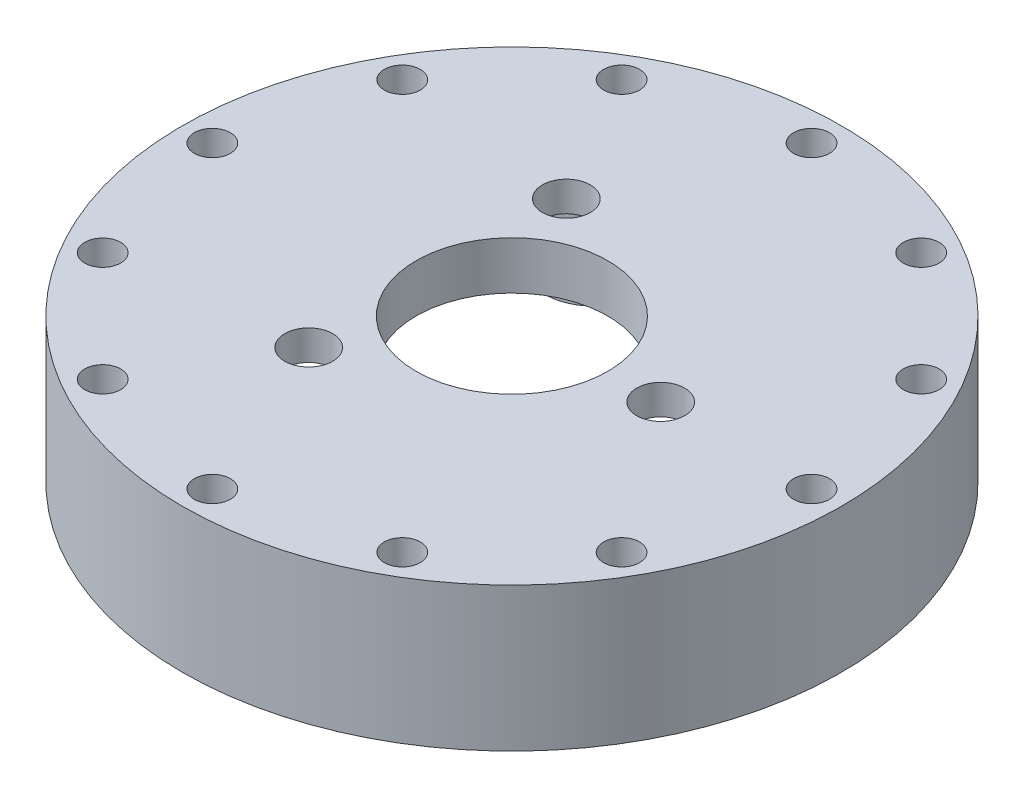
SolidWorks part; units mm, degrees
ref_plane "Front Plane" through (0, 0, 0) normal (0, 0, 1) x (1, 0, 0)
ref_plane "Top Plane" through (0, 0, 0) normal (0, 1, 0) x (1, 0, 0)
ref_plane "Right Plane" through (0, 0, 0) normal (1, 0, 0) x (0, 0, -1)
sketch "Sketch1" plane through (0, 0, 0) normal (0, 1, 0) x (1, 0, 0)
  line L0 (0, 22.5) -> (0, 0) construction
  line L1 (0, 0) -> (12.1644, 18.9282) construction
  line L2 (0, 0) -> (-12.1644, 18.9282) construction
  line L3 (-20.4667, 9.3468) -> (0, 0) construction
  line L4 (0, 0) -> (-22.271, -3.2021) construction
  circle A0 centre (0, 0) radius 22.5
  circle A1 centre (0, 0) radius 27.5
  circle A2 centre (0, 22.5) radius 4
  circle A3 centre (12.1644, 18.9282) radius 4
  circle A4 centre (20.4667, 9.3468) radius 4
  circle A5 centre (22.271, -3.2021) radius 4
  circle A6 centre (17.0044, -14.7344) radius 4
  circle A7 centre (6.339, -21.5886) radius 4
  circle A8 centre (-6.339, -21.5886) radius 4
  circle A9 centre (-17.0044, -14.7344) radius 4
  circle A10 centre (-22.271, -3.2021) radius 4
  circle A11 centre (-20.4667, 9.3468) radius 4
  circle A12 centre (-12.1644, 18.9282) radius 4
  point P27 (0, 0)
  dimension "D1" = 45
  dimension "D2" = 55
  dimension "D3" = 8
  dimension "D4" = 11
extrude "Boss-Extrude2" add sketch "Sketch1" along normal blind 8 contours A1 A12 A0 A2 A3 A4 A5 A6 A7 A8 A9 A10 A11 | A0 A11 | A0 A11 | A0 A12 | A0 A12 | A0 A2 | A0 A2 | A0 A3 | A0 A3 | A0 A4 | A0 A4 | A0 A5 | A0 A5 | A0 A6 | A0 A6 | A0 A7 | A0 A7 | A0 A8 | A0 A8 | A0 A9 | A0 A9 | A0 A10 | A0 A10 | A12 region at (20.5288, 0, 2.9516) region at (23.8864, 0, 3.4343) region at (18.8657, 0, -8.6157) region at (21.9512, 0, -10.0248) region at (18.2378, 0, 15.8031) region at (15.6742, 0, 13.5818) region at (11.2128, 0, -17.4475) region at (13.0467, 0, -20.3011) region at (6.7988, 0, 23.1545) region at (5.8431, 0, 19.8998) region at (0, 0, -20.7399) region at (0, 0, -24.132) region at (-6.7988, 0, 23.1545) region at (-5.8431, 0, 19.8998) region at (-11.2128, 0, -17.4475) region at (-13.0467, 0, -20.3011) region at (-18.2378, 0, 15.8031) region at (-15.6742, 0, 13.5818) region at (-18.8657, 0, -8.6157) region at (-21.9512, 0, -10.0248) region at (-23.8864, 0, 3.4343) region at (-20.5288, 0, 2.9516) region at (-26.7222, 0, 0)
sketch "Sketch2" plane through (0, 8, 0) normal (0, 1, 0) x (1, 0, 0)
  line L1 (12.413, 0) -> (-6.2065, 10.75) construction
  line L2 (-6.2065, 10.75) -> (-6.2065, -10.75) construction
  line L3 (-6.2065, -10.75) -> (12.413, 0) construction
  circle A0 centre (0, 0) radius 27.5
  circle A1 centre (0, 0) radius 8
  circle A2 centre (0, 0) radius 6.2065 construction
  circle A3 centre (-6.2065, 10.75) radius 2
  circle A4 centre (12.413, 0) radius 2
  circle A5 centre (-6.2065, -10.75) radius 2
  point P16 (0, 0)
  dimension "D1" = 16
  dimension "D2" = 55
  dimension "D4" = 4
  dimension "D3" = 21.5
  dimension "D5" = 3
extrude "Boss-Extrude3" add sketch "Sketch2" along normal blind 4
fillet "Fillet2" radius 1 22 edges at (19.3447, 4, 11.4905) (10.0616, 4, 20.125) (2.416, 4, 22.3699) (14.1266, 4, 17.5126) (-2.416, 4, 22.3699) (-10.0616, 4, 20.125) (-14.1266, 4, 17.5126) (-19.3447, 4, 11.4905) (-21.352, 4, 7.0951) (-22.4861, 4, -0.7921) (-21.7984, 4, -5.575) (-18.4882, 4, -12.8233) (-15.3239, 4, -16.4751) (-8.6205, 4, -20.7831) (-3.9842, 4, -22.1444) (3.9842, 4, -22.1444) (8.6205, 4, -20.7831) (15.3239, 4, -16.4751) (18.4882, 4, -12.8233) (21.7984, 4, -5.575) (22.4861, 4, -0.7921) (21.352, 4, 7.0951)
sketch "Sketch8" plane through (0, 0, 0) normal (0, -1, 0) x (1, 0, 0)
  circle A0 centre (0, 0) radius 25 construction
  circle A1 centre (0, -25) radius 1.5
  circle A2 centre (-12.5, -21.6506) radius 1.5
  circle A3 centre (-21.6506, -12.5) radius 1.5
  circle A4 centre (-25, 0) radius 1.5
  circle A5 centre (-21.6506, 12.5) radius 1.5
  circle A6 centre (-12.5, 21.6506) radius 1.5
  circle A7 centre (0, 25) radius 1.5
  circle A8 centre (12.5, 21.6506) radius 1.5
  circle A9 centre (21.6506, 12.5) radius 1.5
  circle A10 centre (25, 0) radius 1.5
  circle A11 centre (21.6506, -12.5) radius 1.5
  circle A12 centre (12.5, -21.6506) radius 1.5
  point P30 (0, 0)
  dimension "D1" = 50
  dimension "D2" = 3
  dimension "D3" = 12
extrude "Cut-Extrude1" cut sketch "Sketch8" against normal through all
sketch "Sketch9" plane through (0, 8, 0) normal (0, -1, 0) x (1, 0, 0)
  circle A0 centre (0, 0) radius 12.413 construction
  circle A1 centre (12.413, 0) radius 4.25
  circle A2 centre (-6.2065, -10.75) radius 4.25
  circle A3 centre (-6.2065, 10.75) radius 4.25
  point P13 (0, 0)
  dimension "D1" = 8.5
  dimension "D2" = 3
extrude "Cut-Extrude2" cut sketch "Sketch9" against normal blind 1.5
